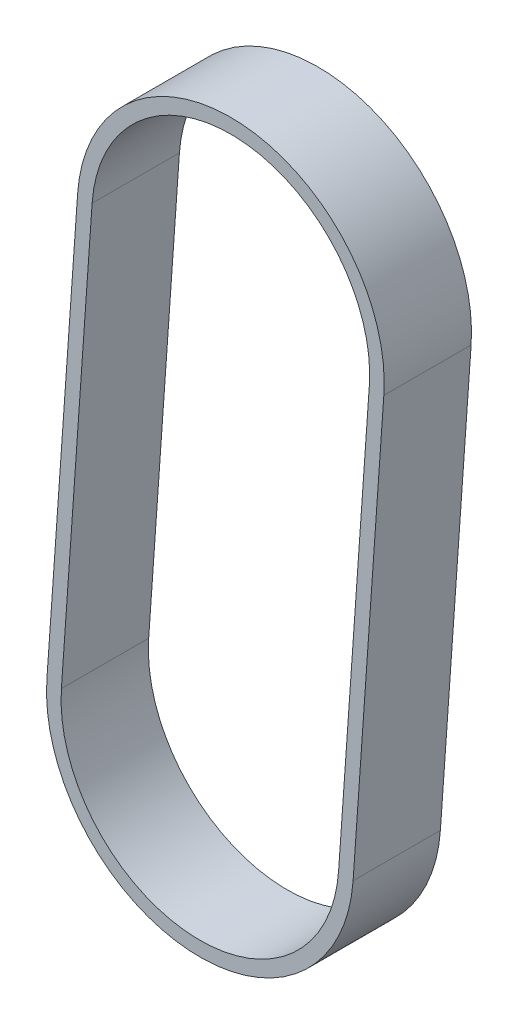
SolidWorks part; units mm, degrees
ref_plane "Front Plane" through (0, 0, 0) normal (0, 0, 1) x (1, 0, 0)
ref_plane "Top Plane" through (0, 0, 0) normal (0, 1, 0) x (1, 0, 0)
ref_plane "Right Plane" through (0, 0, 0) normal (1, 0, 0) x (0, 0, -1)
sketch "Sketch2" plane through (0, 0, 0) normal (0, 0, 1) x (1, 0, 0)
  line L0 (0, 0) -> (1, 0) construction
  line L1 (0, 0) -> (0, 1) construction
  line L4 (-17.457, -43.9121) -> (-14.2884, 1.0079)
  line L5 (14.2884, -1.0079) -> (11.1199, -45.9279)
  arc A2 (11.1199, -45.9279) -> (-17.457, -43.9121) centre (-3.1685, -44.92) cw
  arc A3 (-14.2884, 1.0079) -> (14.2884, -1.0079) centre (0, 0) cw
extrude "Extrude-Thin1" add sketch "Sketch2" along normal blind 9 thin thin type one direction wall 1.5
